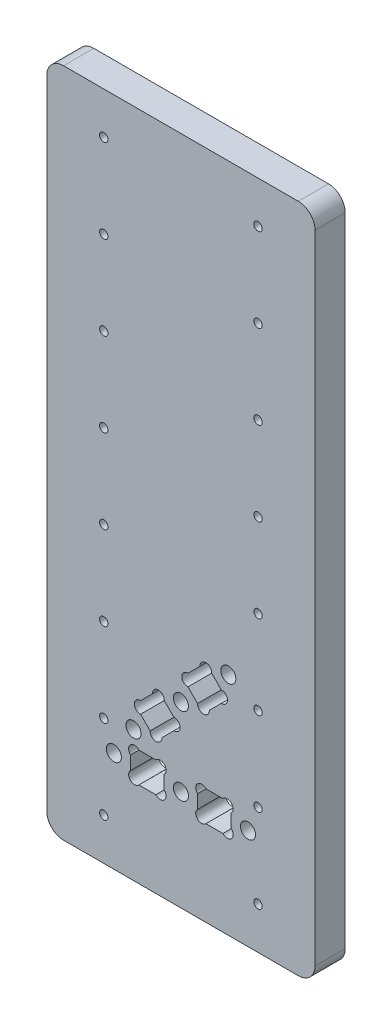
SolidWorks part; units mm, degrees
ref_plane "Plan de face" through (0, 0, 0) normal (0, 0, 1) x (1, 0, 0)
ref_plane "Plan de dessus" through (0, 0, 0) normal (0, 1, 0) x (1, 0, 0)
ref_plane "Plan de droite" through (0, 0, 0) normal (1, 0, 0) x (0, 0, -1)
sketch "Esquisse1" plane through (0, 0, 0) normal (0, 0, 1) x (1, 0, 0)
  line L1 (0, 0) -> (80, 0)
  line L2 (0, 0) -> (0, 200)
  line L3 (0, 200) -> (80, 200)
  line L4 (80, 0) -> (80, 200)
  dimension "D1" = 80
  dimension "D2" = 200
extrude "Boss.-Extru.1" add sketch "Esquisse1" along normal blind 9
sketch "Esquisse2" plane through (0, 0, 9) normal (0, 0, 1) x (1, 0, 0)
  line L0 (40, 0) -> (40, 200) construction
  line L1 (0, 0) -> (80, 0) construction
  line L2 (80, 200) -> (0, 200) construction
  line L3 (17, 0) -> (17, 200) construction
  line L4 (40, 100) -> (0, 100) construction
  line L5 (0, 200) -> (0, 0) construction
  circle A0 centre (17, 187.5) radius 1.25
  circle A1 centre (17, 87.5) radius 1.25
  circle A2 centre (17, 62.5) radius 1.25
  circle A3 centre (17, 37.5) radius 1.25
  circle A4 centre (17, 12.5) radius 1.25
  circle A5 centre (17, 162.5) radius 1.25
  circle A6 centre (17, 137.5) radius 1.25
  circle A7 centre (17, 112.5) radius 1.25
  circle A8 centre (63, 112.5) radius 1.25
  circle A9 centre (63, 137.5) radius 1.25
  circle A10 centre (63, 162.5) radius 1.25
  circle A11 centre (63, 12.5) radius 1.25
  circle A12 centre (63, 37.5) radius 1.25
  circle A13 centre (63, 62.5) radius 1.25
  circle A14 centre (63, 87.5) radius 1.25
  circle A15 centre (63, 187.5) radius 1.25
  dimension "D2" = 2.5
  dimension "D3" = 12.5
  dimension "D4" = 25
  dimension "D5" = 25
  dimension "D1" = 23
  dimension "D6" = 25
extrude "Enlèv. mat.-Extru.1" cut sketch "Esquisse2" against normal through all both and the other way through all
sketch "Esquisse3" plane through (0, 0, 9) normal (0, 0, 1) x (1, 0, 0)
  line L0 (43.182, 0) -> (43.182, 50) construction
  line L2 (43.182, 50) -> (46.7175, 53.5355) construction
  line L3 (46.7175, 53.5355) -> (53.7886, 60.6066)
  line L4 (53.7886, 60.6066) -> (47.4246, 66.9706)
  line L5 (47.4246, 66.9706) -> (40.3536, 59.8995)
  line L6 (40.3536, 59.8995) -> (46.7175, 53.5355)
  line L7 (43.182, 50) -> (32.8481, 60.3339) construction
  line L8 (33.2825, 52.8284) -> (39.6464, 46.4645)
  line L9 (26.2114, 45.7574) -> (33.2825, 52.8284)
  line L10 (32.5754, 39.3934) -> (26.2114, 45.7574)
  line L11 (39.6464, 46.4645) -> (32.5754, 39.3934)
  line L12 (26.2114, 45.7574) -> (17, 45.7574) construction
  line L13 (17, 45.7574) -> (17, 37.5) construction
  line L14 (53.7886, 60.6066) -> (63, 60.6066) construction
  line L15 (63, 60.6066) -> (63, 37.5) construction
  line L16 (0, 0) -> (80, 0) construction
  point P17 (17, 33.3933)
  point P18 (43.182, 0)
  dimension "D1" = 135
  dimension "D2" = 9
  dimension "D3" = 10
  dimension "D4" = 5
  dimension "D5" = 50
extrude "Enlèv. mat.-Extru.2" cut sketch "Esquisse3" against normal through all both and the other way through all
fillet "Congé1" radius 5 4 edges at (0, 200, 4.5) (80, 200, 4.5) (80, 0, 4.5) (0, 0, 4.5)
sketch "Esquisse4" plane through (0, 0, 9) normal (0, 0, 1) x (1, 0, 0)
  line L0 (32.5754, 39.3934) -> (26.2114, 45.7574) construction
  line L1 (26.2114, 45.7574) -> (33.2825, 52.8284) construction
  line L2 (27.8641, 45.7574) -> (26.2114, 45.7574) construction
  line L3 (27.9614, 47.5074) -> (27.9614, 44.0074)
  line L4 (26.2114, 45.7574) -> (26.1114, 45.7574) construction
  line L5 (29.3934, 42.5754) -> (36.4645, 49.6464) construction
  line L6 (33.2825, 52.8284) -> (39.6464, 46.4645) construction
  line L7 (29.747, 49.2929) -> (36.1109, 42.9289) construction
  line L8 (39.6464, 46.4645) -> (32.5754, 39.3934) construction
  line L9 (33.2825, 52.8284) -> (33.2825, 52.9284) construction
  line L10 (33.2825, 51.1757) -> (33.2825, 52.8284) construction
  line L11 (31.5325, 51.0784) -> (35.0325, 51.0784)
  line L12 (37.9937, 46.4645) -> (39.6464, 46.4645) construction
  line L13 (39.6464, 46.4645) -> (39.7464, 46.4645) construction
  line L14 (32.5754, 39.3934) -> (32.5754, 39.2934) construction
  line L15 (32.5754, 41.0461) -> (32.5754, 39.3934) construction
  line L16 (37.8964, 44.7145) -> (37.8964, 48.2145)
  line L17 (34.3254, 41.1434) -> (30.8254, 41.1434)
  line L18 (36.4645, 49.6464) -> (43.5355, 56.7175) construction
  line L19 (46.7175, 53.5355) -> (40.3536, 59.8995) construction
  line L20 (40, 53.182) -> (41.6519, 51.5301) construction
  line L21 (52.1359, 60.6066) -> (53.7886, 60.6066) construction
  line L22 (53.7886, 60.6066) -> (53.8886, 60.6066) construction
  line L23 (46.7175, 53.5355) -> (46.7175, 53.4355) construction
  line L24 (46.7175, 55.1882) -> (46.7175, 53.5355) construction
  line L25 (42.0063, 59.8995) -> (40.3536, 59.8995) construction
  line L26 (40.3536, 59.8995) -> (40.2536, 59.8995) construction
  line L27 (43.8891, 63.435) -> (50.253, 57.0711) construction
  line L28 (50.6066, 63.7886) -> (43.5355, 56.7175) construction
  line L29 (47.4246, 66.9706) -> (47.4246, 67.0706) construction
  line L30 (47.4246, 65.3179) -> (47.4246, 66.9706) construction
  line L31 (52.0386, 58.8566) -> (52.0386, 62.3566)
  line L32 (48.4675, 55.2855) -> (44.9675, 55.2855)
  line L33 (42.1036, 61.6495) -> (42.1036, 58.1495)
  line L34 (45.6746, 65.2206) -> (49.1746, 65.2206)
  line L35 (29.3934, 42.5754) -> (25.8579, 39.0398) construction
  arc A0 (27.9614, 44.0074) -> (27.9614, 47.5074) centre (27.8641, 45.7574) cw
  arc A1 (35.0325, 51.0784) -> (31.5325, 51.0784) centre (33.2825, 51.1757) ccw
  arc A2 (37.8964, 48.2145) -> (37.8964, 44.7145) centre (37.9937, 46.4645) cw
  arc A3 (30.8254, 41.1434) -> (34.3254, 41.1434) centre (32.5754, 41.0461) ccw
  arc A4 (52.0386, 62.3566) -> (52.0386, 58.8566) centre (52.1359, 60.6066) cw
  arc A5 (44.9675, 55.2855) -> (48.4675, 55.2855) centre (46.7175, 55.1882) ccw
  arc A6 (42.1036, 58.1495) -> (42.1036, 61.6495) centre (42.0063, 59.8995) cw
  arc A7 (49.1746, 65.2206) -> (45.6746, 65.2206) centre (47.4246, 65.3179) ccw
  circle A8 centre (40, 53.182) radius 2.25
  circle A9 centre (25.8579, 39.0398) radius 2.25
  circle A10 centre (54.1421, 67.3241) radius 2.25
  dimension "D2" = 3.5
  dimension "D3" = 5
  dimension "D4" = 4.5
  dimension "D1" = 0.1
extrude "Enlèv. mat.-Extru.3" cut sketch "Esquisse4" against normal through all both and the other way through all
sketch "Esquisse5" plane through (0, 0, 9) normal (0, 0, 1) x (1, 0, 0)
  line L0 (52.0386, 58.8566) -> (48.4675, 55.2855) construction
  line L1 (49.1746, 65.2206) -> (52.0386, 62.3566) construction
  line L2 (42.1036, 61.6495) -> (45.6746, 65.2206) construction
  line L3 (44.9675, 55.2855) -> (42.1036, 58.1495) construction
  line L4 (37.8964, 44.7145) -> (34.3254, 41.1434) construction
  line L5 (35.0325, 51.0784) -> (37.8964, 48.2145) construction
  line L6 (27.9614, 47.5074) -> (31.5325, 51.0784) construction
  line L7 (30.8254, 41.1434) -> (27.9614, 44.0074) construction
  line L8 (52.0386, 58.8566) -> (48.4675, 55.2855) construction
  line L9 (49.1746, 65.2206) -> (52.0386, 62.3566) construction
  line L10 (42.1036, 61.6495) -> (45.6746, 65.2206) construction
  line L11 (44.9675, 55.2855) -> (42.1036, 58.1495) construction
  line L12 (37.8964, 44.7145) -> (34.3254, 41.1434) construction
  line L13 (35.0325, 51.0784) -> (37.8964, 48.2145) construction
  line L14 (27.9614, 47.5074) -> (31.5325, 51.0784) construction
  line L15 (30.8254, 41.1434) -> (27.9614, 44.0074) construction
  line L16 (54.1421, 67.3241) -> (40, 53.182) construction
  line L17 (54.1421, 67.3241) -> (12.0169, 41.591) construction
  line L18 (52.5251, 25.5) -> (47.4749, 25.5)
  line L19 (55, 32.0251) -> (55, 27.9749)
  line L20 (47.4749, 34.5) -> (52.5251, 34.5)
  line L21 (45, 27.9749) -> (45, 32.0251)
  line L22 (32.5251, 25.5) -> (27.4749, 25.5)
  line L23 (35, 32.0251) -> (35, 27.9749)
  line L24 (27.4749, 34.5) -> (32.5251, 34.5)
  line L25 (25, 27.9749) -> (25, 32.0251)
  line L26 (60, 30) -> (40, 30) construction
  line L27 (40, 30) -> (40, 0) construction
  line L29 (5, 0) -> (75, 0) construction
  circle A0 centre (54.1421, 67.3241) radius 2.25 construction
  arc A1 (52.0386, 58.8566) -> (52.0386, 62.3566) centre (52.1359, 60.6066) ccw construction
  arc A2 (49.1746, 65.2206) -> (45.6746, 65.2206) centre (47.4246, 65.3179) ccw construction
  arc A3 (42.1036, 61.6495) -> (42.1036, 58.1495) centre (42.0063, 59.8995) ccw construction
  arc A4 (44.9675, 55.2855) -> (48.4675, 55.2855) centre (46.7175, 55.1882) ccw construction
  circle A5 centre (40, 53.182) radius 2.25 construction
  circle A6 centre (25.8579, 39.0398) radius 2.25 construction
  arc A7 (30.8254, 41.1434) -> (34.3254, 41.1434) centre (32.5754, 41.0461) ccw construction
  arc A8 (37.8964, 44.7145) -> (37.8964, 48.2145) centre (37.9937, 46.4645) ccw construction
  arc A9 (35.0325, 51.0784) -> (31.5325, 51.0784) centre (33.2825, 51.1757) ccw construction
  arc A10 (27.9614, 47.5074) -> (27.9614, 44.0074) centre (27.8641, 45.7574) ccw construction
  circle A11 centre (54.1421, 67.3241) radius 2.25 construction
  arc A12 (52.0386, 58.8566) -> (52.0386, 62.3566) centre (52.1359, 60.6066) ccw construction
  arc A13 (49.1746, 65.2206) -> (45.6746, 65.2206) centre (47.4246, 65.3179) ccw construction
  arc A14 (42.1036, 61.6495) -> (42.1036, 58.1495) centre (42.0063, 59.8995) ccw construction
  arc A15 (44.9675, 55.2855) -> (48.4675, 55.2855) centre (46.7175, 55.1882) ccw construction
  circle A16 centre (40, 53.182) radius 2.25 construction
  circle A17 centre (25.8579, 39.0398) radius 2.25 construction
  arc A18 (30.8254, 41.1434) -> (34.3254, 41.1434) centre (32.5754, 41.0461) ccw construction
  arc A19 (37.8964, 44.7145) -> (37.8964, 48.2145) centre (37.9937, 46.4645) ccw construction
  arc A20 (35.0325, 51.0784) -> (31.5325, 51.0784) centre (33.2825, 51.1757) ccw construction
  arc A21 (27.9614, 47.5074) -> (27.9614, 44.0074) centre (27.8641, 45.7574) ccw construction
  circle A22 centre (60, 30) radius 2.25
  arc A23 (52.5251, 25.5) -> (55, 27.9749) centre (53.8314, 26.6686) ccw
  arc A24 (55, 32.0251) -> (52.5251, 34.5) centre (53.8314, 33.3314) ccw
  arc A25 (47.4749, 34.5) -> (45, 32.0251) centre (46.1686, 33.3314) ccw
  arc A26 (45, 27.9749) -> (47.4749, 25.5) centre (46.1686, 26.6686) ccw
  circle A27 centre (40, 30) radius 2.25
  circle A28 centre (20, 30) radius 2.25
  arc A29 (25, 27.9749) -> (27.4749, 25.5) centre (26.1686, 26.6686) ccw
  arc A30 (32.5251, 25.5) -> (35, 27.9749) centre (33.8314, 26.6686) ccw
  arc A31 (35, 32.0251) -> (32.5251, 34.5) centre (33.8314, 33.3314) ccw
  arc A32 (27.4749, 34.5) -> (25, 32.0251) centre (26.1686, 33.3314) ccw
  point P66 (12.0169, 41.591)
  dimension "D1" = 30
  dimension "D3" = 45
  dimension "D2" = 2
extrude "Enlèv. mat.-Extru.4" cut sketch "Esquisse5" against normal through all both and the other way through all
